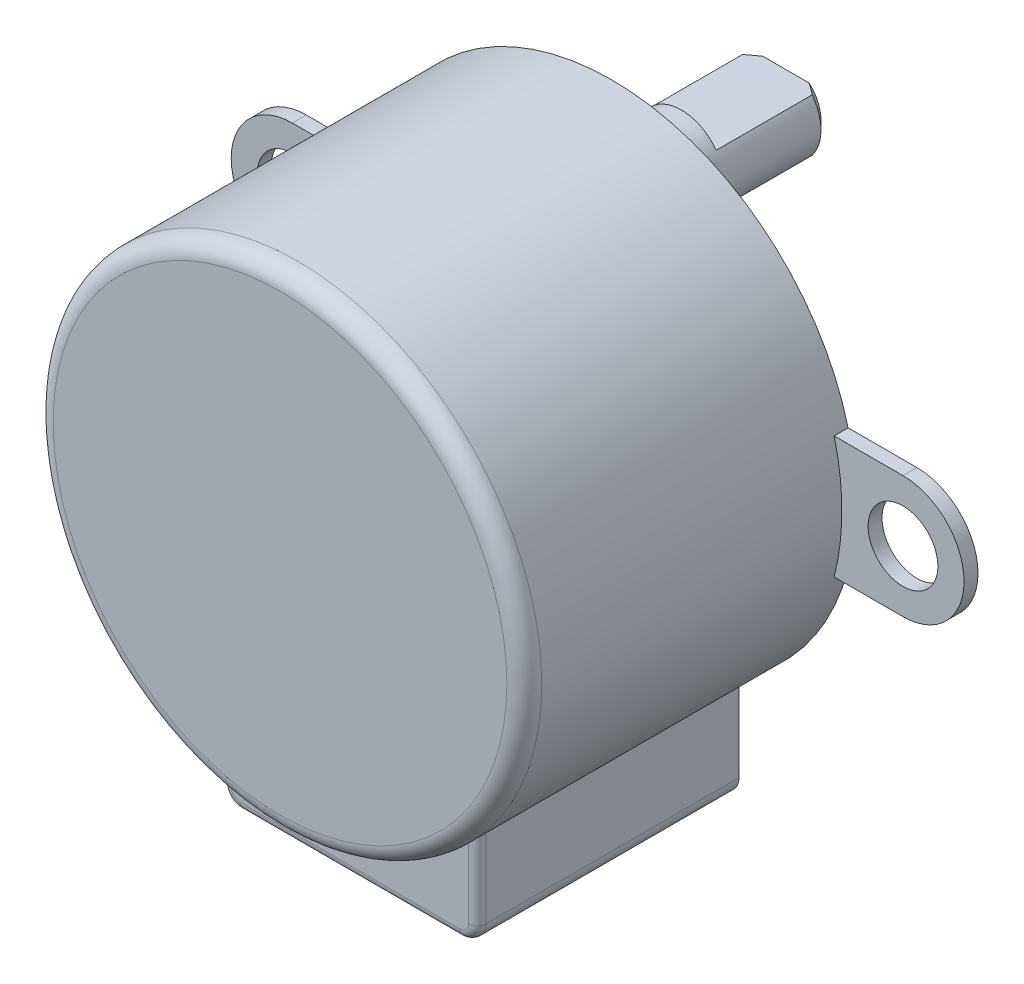
SolidWorks part; units mm, degrees
ref_plane "前视基准面" through (0, 0, 0) normal (0, 0, 1) x (1, 0, 0)
ref_plane "上视基准面" through (0, 0, 0) normal (0, 1, 0) x (1, 0, 0)
ref_plane "右视基准面" through (0, 0, 0) normal (1, 0, 0) x (0, 0, -1)
sketch "草图1" plane through (0, 0, 0) normal (0, 0, 1) x (1, 0, 0)
  circle A0 centre (0, 0) radius 14
  dimension "D1" = 28
extrude "凸台-拉伸1" add sketch "草图1" along normal blind 19
sketch "草图2" plane through (0, 0, 0) normal (0, 0, 1) x (1, 0, 0)
  line L0 (0, 20.4901) -> (0, -22.3048) construction
  line L1 (-24.8056, 0) -> (23.1683, 0) construction
  line L2 (-17.5, 3.5) -> (17.5, 3.5)
  line L3 (-17.5, -3.5) -> (17.5, -3.5)
  circle A0 centre (-17.5, 0) radius 2
  circle A1 centre (17.5, 0) radius 2
  arc A2 (-17.5, 3.5) -> (-17.5, -3.5) centre (-17.5, 0) ccw
  arc A3 (17.5, 3.5) -> (17.5, -3.5) centre (17.5, 0) cw
  dimension "D1" = 4
  dimension "D3" = 7
  dimension "D2" = 35
extrude "凸台-拉伸2" add sketch "草图2" along normal blind 0.8
sketch "草图3" plane through (0, 0, 0) normal (0, 0, -1) x (-1, 0, 0)
  circle A0 centre (0, 8) radius 4.5
  dimension "D1" = 9
  dimension "D2" = 8
extrude "凸台-拉伸3" add sketch "草图3" along normal blind 1.5
sketch "草图4" plane through (0, 0, -1.5) normal (0, 0, -1) x (-1, 0, 0)
  circle A0 centre (0, 8) radius 2.5
  dimension "D1" = 5
extrude "凸台-拉伸4" add sketch "草图4" along normal blind 8.5
sketch "草图5" plane through (0, 0, -10) normal (0, 0, -1) x (-1, 0, 0)
  line L1 (-6.1682, 6.5) -> (6.1682, 6.5)
  line L2 (-6.1682, 6.5) -> (-6.1682, 9.5)
  line L3 (-6.1682, 9.5) -> (6.1682, 9.5)
  line L4 (6.1682, 6.5) -> (6.1682, 9.5)
  line L5 (-6.1682, 6.5) -> (6.1682, 9.5) construction
  line L6 (-6.1682, 9.5) -> (6.1682, 6.5) construction
  point P0 (0, 8)
  dimension "D1" = 3
extrude "切除-拉伸1" cut sketch "草图5" against normal blind 6 flip side to cut
chamfer "倒角2" distance 0.5 angle 45 2 edges at (2.5, 8, -10) (-2.5, 8, -10)
sketch "草图6" plane through (0, 0, 0) normal (0, 0, -1) x (-1, 0, 0)
  line L0 (-24.1726, 0) -> (27.6734, 0) construction
  line L1 (0, 15.9206) -> (0, -16.4207) construction
  line L2 (-7.3, -9.4979) -> (7.3, -9.4979)
  line L3 (-7.3, -9.4979) -> (-7.3, -18)
  line L4 (-7.3, -18) -> (7.3, -18)
  line L5 (7.3, -9.4979) -> (7.3, -18)
  dimension "D1" = 18
  dimension "D2" = 14.6
extrude "凸台-拉伸5" add sketch "草图6" against normal blind 15
sketch "草图7" plane through (0, 0, 0) normal (0, 0, -1) x (-1, 0, 0)
  line L1 (-6.3, -11.3715) -> (-6.3, -17)
  line L2 (-6.3, -17) -> (6.3, -17)
  line L3 (-7.3, -11.9461) -> (-7.3, -18) construction
  line L4 (-7.3, -18) -> (7.3, -18) construction
  line L5 (6.3, -11.3715) -> (6.3, -17)
  arc A0 (6.3, -11.3715) -> (-6.3, -11.3715) centre (0, 0) ccw
  point P12 (0, -17)
  dimension "D1" = 26
  dimension "D2" = 1
  dimension "D3" = 1
split line "分割线1"
fillet "圆角1" radius 1 2 edges at (-7.3, -18, 7.5) (7.3, -18, 7.5)
fillet "圆角3" radius 1 1 edges at (14, 0, 19)
fillet "圆角4" radius 0.5 1 edges at (-4.5, 8, -1.5)
sketch "草图8" plane through (0, 0, 0) normal (0, 0, -1) x (-1, 0, 0)
  line L0 (-7.3, -11.9461) -> (-7.3, -10.7569)
  line L1 (7.3, -11.9461) -> (7.3, -10.7569)
  line L2 (6.3, -17) -> (6.3, -11.3715) construction
  line L3 (-6.3, -17) -> (6.3, -17) construction
  line L4 (-6.3, -11.3715) -> (-6.3, -17) construction
  line L5 (6.3, -17) -> (6.3, -11.3715)
  line L6 (-6.3, -17) -> (6.3, -17)
  line L7 (-6.3, -11.3715) -> (-6.3, -17)
  line L8 (7.3, -17) -> (7.3, -11.9461) construction
  line L9 (-6.3, -18) -> (6.3, -18) construction
  line L10 (-7.3, -11.9461) -> (-7.3, -17) construction
  line L11 (7.3, -17) -> (7.3, -11.9461)
  line L12 (-6.3, -18) -> (6.3, -18)
  line L13 (-7.3, -11.9461) -> (-7.3, -17)
  arc A0 (6.3, -11.3715) -> (-6.3, -11.3715) centre (0, 0) ccw construction
  arc A1 (6.3, -11.3715) -> (7.3, -10.7569) centre (0, 0) ccw
  arc A2 (-7.3, -10.7569) -> (-6.3, -11.3715) centre (0, 0) ccw
  arc A3 (6.3, -18) -> (7.3, -17) centre (6.3, -17) ccw construction
  arc A4 (-7.3, -17) -> (-6.3, -18) centre (-6.3, -17) ccw construction
  arc A5 (6.3, -18) -> (7.3, -17) centre (6.3, -17) ccw
  arc A6 (-7.3, -17) -> (-6.3, -18) centre (-6.3, -17) ccw
split line "分割线2"
fillet "圆角5" radius 0.5 8 edges at (7.3, -11.9461, 7.5) (-7.3, -11.9461, 7.5) (0, -14, 15) (7.3, -14.4731, 15) (7.0071, -17.7071, 15) (0, -18, 15) (-7.0071, -17.7071, 15) (-7.3, -14.4731, 15)
sketch "Sketch1" plane through (0, 0, 0) normal (0, 0, 1) x (1, 0, 0)
  line L0 (6.3, -11.3715) -> (6.3, -17) construction
  line L1 (6.3, -17) -> (-6.3, -17) construction
  line L2 (6.3, -11.3715) -> (6.3, -17)
  line L3 (6.3, -17) -> (-6.3, -17)
  line L4 (7.3, -12.2233) -> (7.3, -17) construction
  line L5 (7.3, -12.2233) -> (7.3, -17)
  line L6 (-7.3, -17) -> (-7.3, -12.2233) construction
  line L7 (-7.3, -17) -> (-7.3, -12.2233)
  line L10 (1.3229, 9.5) -> (-1.3229, 9.5)
  line L11 (-1.3229, 6.5) -> (1.3229, 6.5)
  line L12 (1.3229, 9.5) -> (-1.3229, 9.5)
  line L13 (-1.3229, 6.5) -> (1.3229, 6.5)
  arc A0 (17.5, -3.5) -> (17.5, 3.5) centre (17.5, 0) ccw construction
  arc A1 (-17.5, 3.5) -> (-17.5, -3.5) centre (-17.5, 0) ccw construction
  circle A2 centre (0, 8) radius 4.5 construction
  arc A3 (13.5554, 3.5) -> (-13.5554, 3.5) centre (0, 0) ccw construction
  circle A4 centre (17.5, 0) radius 2 construction
  arc A5 (17.5, -3.5) -> (17.5, 3.5) centre (17.5, 0) ccw
  arc A6 (-17.5, 3.5) -> (-17.5, -3.5) centre (-17.5, 0) ccw
  circle A7 centre (0, 8) radius 4.5
  arc A8 (13.5554, 3.5) -> (-13.5554, 3.5) centre (0, 0) ccw
  circle A9 centre (17.5, 0) radius 2
  circle A10 centre (0, 8) radius 2.5 construction
  circle A11 centre (0, 8) radius 2.5
  arc A14 (1.3229, 6.5) -> (1.3229, 9.5) centre (0, 8) ccw
  arc A15 (-1.3229, 9.5) -> (-1.3229, 6.5) centre (0, 8) ccw
  arc A16 (1.3229, 6.5) -> (1.3229, 9.5) centre (0, 8) ccw
  arc A17 (-1.3229, 9.5) -> (-1.3229, 6.5) centre (0, 8) ccw
  point P18 (21, 0)
  point P19 (-21, 0)
  dimension "D2" = 14
  dimension "D3" = 4
  dimension "D11" = 3.5
  dimension "D12" = 5
  dimension "D15" = 2
  dimension "D1" = 42
  dimension "D4" = 3.9446
  dimension "D5" = 17.5
  dimension "D6" = 8
  dimension "D7" = 12.6
  dimension "D8" = 4.7767
  dimension "D9" = 14.6
  dimension "D10" = 8
  dimension "D14" = 3
  dimension "D13" = 0
sketch "Sketch2" plane through (0, 0, 0) normal (1, 0, 0) x (0, 0, -1)
  line L0 (0, -18) -> (-14.5, -18) construction
  line L1 (1.5, 5.5) -> (4, 5.5) construction
  line L2 (4, 10.5) -> (1.5, 10.5) construction
  line L3 (10, 6.5) -> (10, 9.5) construction
  line L4 (0, 12.5) -> (0, 3.5) construction
  line L5 (-19, 13) -> (-19, -13) construction
  line L6 (0, -18) -> (-14.5, -18)
  line L7 (1.5, 5.5) -> (4, 5.5)
  line L8 (4, 10.5) -> (1.5, 10.5)
  line L9 (10, 6.5) -> (10, 9.5)
  line L10 (0, 12.5) -> (0, 3.5)
  line L11 (-19, 13) -> (-19, -13)
  line L12 (-15, -17) -> (-15, -12.8066) construction
  line L13 (-15, -17) -> (-15, -12.8066)
  line L14 (-0.8, 3.5) -> (-0.8, -3.5) construction
  line L15 (-0.8, 3.5) -> (-0.8, -3.5)
  line L16 (-18, -14) -> (-18, 14) construction
  line L17 (-18, -14) -> (-18, 14)
  line L22 (0, -3.5) -> (0, 3.5)
  line L23 (0, 3.5) -> (-0.8, 3.5)
  line L24 (-0.8, 3.5) -> (-0.8, -3.5)
  line L25 (-0.8, -3.5) -> (0, -3.5)
  line L26 (0, -3.5) -> (0, 3.5)
  line L27 (0, 3.5) -> (-0.8, 3.5)
  line L28 (-0.8, 3.5) -> (-0.8, -3.5)
  line L29 (-0.8, -3.5) -> (0, -3.5)
  dimension "D1" = 19
  dimension "D2" = 3
  dimension "D3" = 15
  dimension "D4" = 18.2
  dimension "D5" = 28
  dimension "D7" = 0.8
  dimension "D6" = 0
